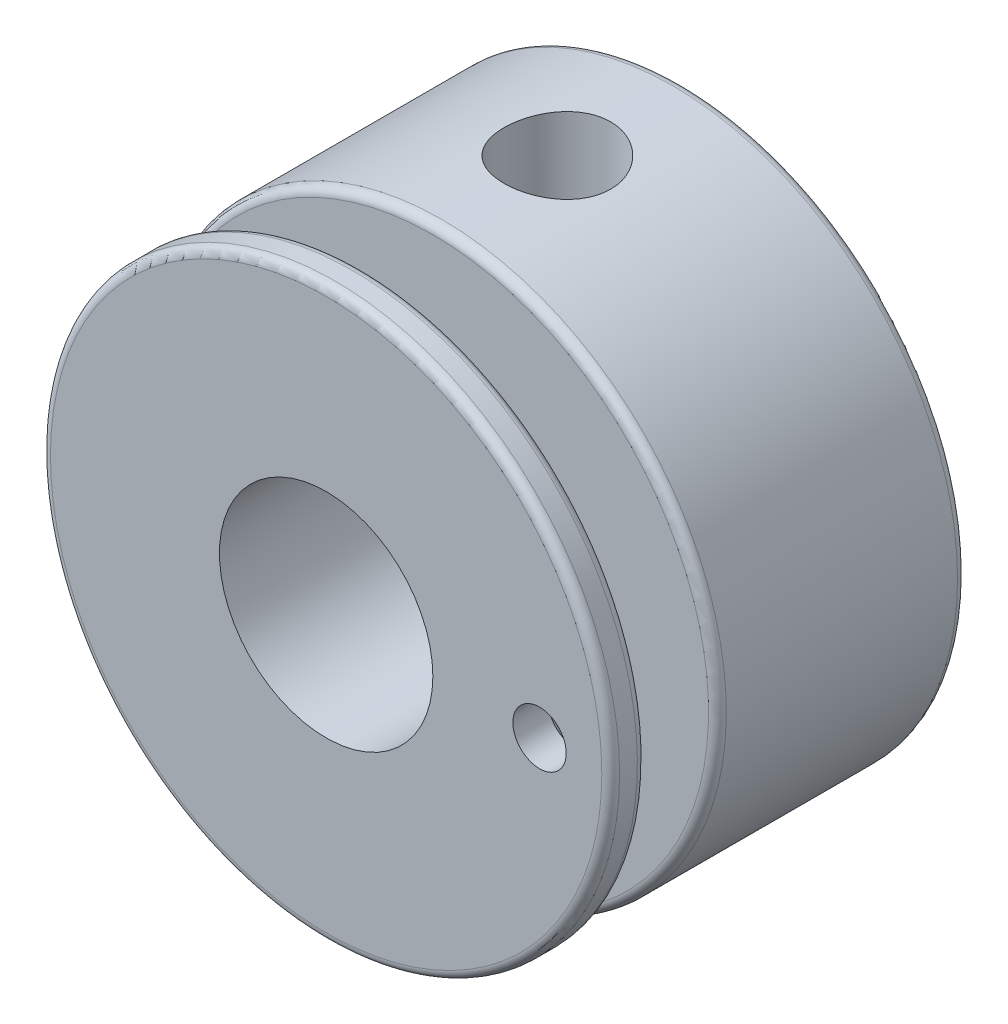
SolidWorks part; units mm, degrees
ref_plane "Front Plane" through (0, 0, 0) normal (0, 0, 1) x (1, 0, 0)
ref_plane "Top Plane" through (0, 0, 0) normal (0, 1, 0) x (1, 0, 0)
ref_plane "Right Plane" through (0, 0, 0) normal (1, 0, 0) x (0, 0, -1)
sketch "Sketch1" plane through (0, 0, 0) normal (0, 0, 1) x (1, 0, 0)
  circle A0 centre (0, 0) radius 8
  dimension "D1" = 16
extrude "Boss-Extrude1" add sketch "Sketch1" along normal blind 10 contours A0
sketch "Sketch2" plane through (0, 0, 0) normal (1, 0, 0) x (0, 0, -1)
  line L0 (0, 8) -> (-10, 8) construction
  line L1 (-9, 8) -> (-7, 8)
  line L2 (-9, 8) -> (-9, 5)
  line L3 (-9, 5) -> (-7, 5)
  line L4 (-7, 8) -> (-7, 5)
  line L5 (-10, 8) -> (-10, -8) construction
  dimension "D1" = 3
  dimension "D2" = 0
  dimension "D3" = 2
  dimension "D4" = 1
sketch "Sketch3" plane through (0, 0, 0) normal (1, 0, 0) x (0, 0, -1)
  line L0 (5.2495, 0) -> (-14.7505, 0)
  dimension "D1" = 20
revolve "Cut-Revolve2" cut sketch "Sketch2" angle 360 about L0
sketch "Sketch5" plane through (0, 0, 0) normal (0, 1, 0) x (1, 0, 0)
  line L1 (0, 5.2495) -> (0, -14.7505) construction
  line L2 (8, 0) -> (-8, 0) construction
  circle A1 centre (0, -3.5) radius 1.5
  dimension "D1" = 3
  dimension "D2" = 3.5
extrude "Cut-Extrude1" cut sketch "Sketch5" along normal up to next from offset 2.5 contours A1
sketch "Sketch6" plane through (0, 0, 0) normal (0, 0, 1) x (1, 0, 0)
  circle A0 centre (0, 0) radius 3
  dimension "D1" = 6
extrude "Cut-Extrude2" cut sketch "Sketch6" along normal up to next
fillet "Fillet3" radius 0.25 1 edges at (0, 8, 9)
fillet "Fillet4" radius 0.25 1 edges at (0, 8, 7)
fillet "Fillet5" radius 0.25 2 edges at (8, 0, 0) (8, 0, 10)
sketch "Sketch7" plane through (0, 0, 10) normal (0, 0, 1) x (1, 0, 0)
  line L0 (-7.75, 0) -> (7.75, 0) construction
  circle A0 centre (0, 0) radius 7.75 construction
  circle A1 centre (6, 0) radius 0.75
  dimension "D1" = 1.5
  dimension "D2" = 1.75
extrude "Cut-Extrude3" cut sketch "Sketch7" against normal up to next
